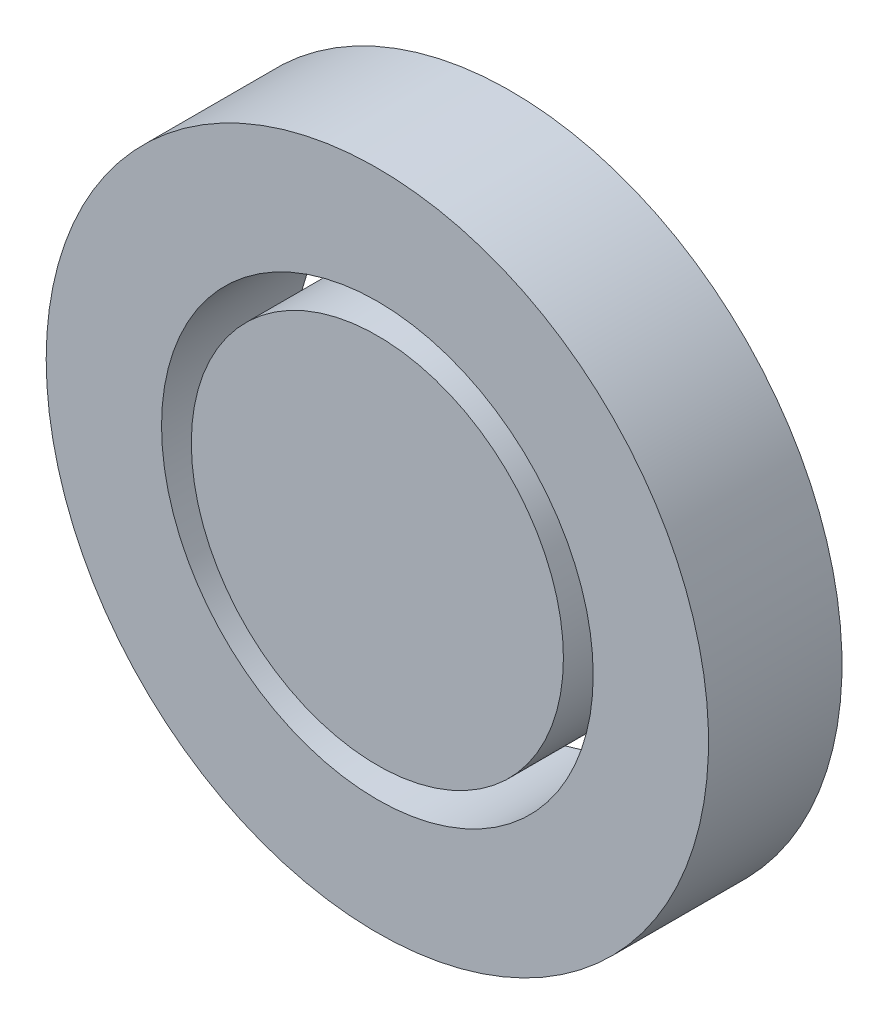
SolidWorks part; units mm, degrees
material "Boron"
ref_plane "Front" through (0, 0, 0) normal (0, 0, 1) x (1, 0, 0)
ref_plane "Top" through (0, 0, 0) normal (0, 1, 0) x (1, 0, 0)
ref_plane "Right" through (0, 0, 0) normal (1, 0, 0) x (0, 0, -1)
sketch "Sketch1" plane through (0, 0, 0) normal (0, 0, 1) x (1, 0, 0)
  circle A0 centre (0, 0) radius 133.5
  circle A1 centre (0, 0) radius 87
  circle A2 centre (0, 0) radius 75
extrude "Boss-Extrude1" add sketch "Sketch1" along normal blind 53.8 contours A2
extrude "Boss-Extrude2" add sketch "Sketch1<3>" along normal blind 53.8 separate body contours A0 | A1
sketch "Sketch1<3>" plane through (0, 0, 0) normal (0, 0, 1) x (1, 0, 0) same geometry as "Sketch1"
